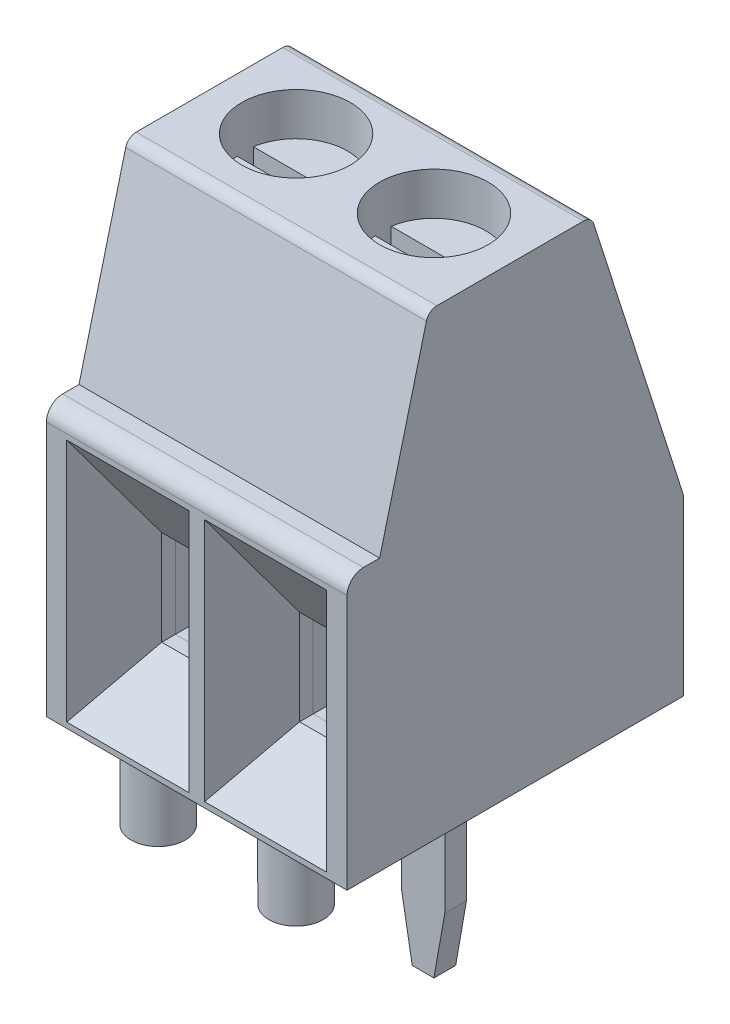
SolidWorks part; units mm, degrees
ref_plane "Plan de face" through (0, 0, 0) normal (0, 0, 1) x (1, 0, 0)
ref_plane "Plan de dessus" through (0, 0, 0) normal (0, 1, 0) x (1, 0, 0)
ref_plane "Plan de droite" through (0, 0, 0) normal (1, 0, 0) x (0, 0, -1)
sketch "Esquisse4" plane through (0, 0, 0) normal (1, 0, 0) x (0, 0, -1)
  line L0 (-3.1, 0) -> (3.1, 0)
  line L1 (3.1, 0) -> (3.1, 3.2)
  line L2 (3.1, 3.2) -> (1.4446, 8.3611)
  line L3 (1.2541, 8.5) -> (-1.4449, 8.5)
  line L4 (-1.6386, 8.3498) -> (-2.5, 5)
  line L5 (-2.5, 5) -> (-2.8, 5)
  line L6 (-3.1, 4.7) -> (-3.1, 0)
  arc A0 (-2.8, 5) -> (-3.1, 4.7) centre (-2.8, 4.7) ccw
  arc A1 (-1.4449, 8.5) -> (-1.6386, 8.3498) centre (-1.4449, 8.3) ccw
  arc A2 (1.4446, 8.3611) -> (1.2541, 8.5) centre (1.2541, 8.3) ccw
  point P11 (-3.1, 5)
  point P14 (-1.6, 8.5)
  point P17 (1.4, 8.5)
  dimension "D9" = 0.3
  dimension "D10" = 0.2
  dimension "D1" = 3.1
  dimension "D2" = 6.2
  dimension "D3" = 8.5
  dimension "D4" = 3.2
  dimension "D5" = 5
  dimension "D6" = 0.6
  dimension "D7" = 1.5
  dimension "D8" = 4.5
extrude "Extrusion2" add sketch "Esquisse4" along normal blind 2.77
sketch "Esquisse5" plane through (0, 0, 0) normal (0, -1, 0) x (1, 0, 0)
  line L0 (0, 3.1) -> (0, -3.1) construction
  line L1 (0.5, 1.6) -> (2.5, 1.6)
  line L2 (0.5, 1.6) -> (0.5, -1.65)
  line L3 (0.5, -1.65) -> (2.5, -1.65)
  line L4 (2.5, 1.6) -> (2.5, -1.65)
  line L5 (2.77, 3.1) -> (0, 3.1) construction
  point P4 (1.5, 1.6)
  dimension "D1" = 1.5
  dimension "D2" = 3.25
  dimension "D3" = 1.5
  dimension "D4" = 2
extrude "Extrusion3" cut sketch "Esquisse5" against normal blind 6.5
hole_wizard "Chambrage pour vis à tête hexagonale M31" positions "Esquisse3D1" profile "Esquisse6" counterbore size "M3" standard "ISO" end condition through all
sketch3d "Esquisse3D1"
  point P0 (1.5, 8.5, 0)
  dimension "D1" = 1.5
sketch "Esquisse6" plane through (1.5, 8.5, 0) normal (1, 0, 0) x (0, 0, 1)
  line L0 (0, 0) -> (0, 8.5)
  line L1 (0, 8.5) -> (0.75, 8.5)
  line L3 (0.75, 8.5) -> (0.75, 1.5)
  line L4 (0.75, 1.5) -> (1, 1.5)
  line L5 (1, 1.5) -> (1, 0)
  line L7 (1, 0) -> (0, 0)
  line L11 (0, -6.35) -> (0, 107.95) construction
  dimension "Diamètre du perçage jusqu'au prochain" = 1.5
  dimension "Profondeur du perçage jusqu'au prochain" = 8.5
  dimension "Diamètre du chambrage" = 2
  dimension "Profondeur du chambrage" = 1.5
sketch "Esquisse7" plane through (0, 0, 3.1) normal (0, 0, 1) x (1, 0, 0)
  line L0 (0, 4.7) -> (0, 0) construction
  line L1 (0.375, 4.6) -> (2.625, 4.6)
  line L2 (0.375, 4.6) -> (0.375, 0.1)
  line L3 (0.375, 0.1) -> (2.625, 0.1)
  line L4 (2.625, 4.6) -> (2.625, 0.1)
  line L5 (2.77, 0) -> (0, 0) construction
  point P4 (1.5, 0.1)
  dimension "D1" = 1.5
  dimension "D2" = 0.1
  dimension "D3" = 2.25
  dimension "D4" = 4.5
ref_plane "Plan1" through (0, 0, 1.85) normal (0, 0, -1) x (-1, 0, 0)
sketch "Esquisse8" plane through (0, 0, 1.85) normal (0, 0, -1) x (-1, 0, 0)
  line L1 (-0.875, 2.75) -> (-2.125, 2.75)
  line L2 (-0.875, 2.75) -> (-0.875, 1)
  line L3 (-0.875, 1) -> (-2.125, 1)
  line L4 (-2.125, 2.75) -> (-2.125, 1)
  line L5 (0, 4.7) -> (0, 0) construction
  line L6 (-2.77, 0) -> (0, 0) construction
  point P4 (-1.5, 1)
  dimension "D1" = 1.5
  dimension "D2" = 1.25
  dimension "D3" = 1.75
  dimension "D4" = 1
loft "Enlèvement de matière-Lissage1" cut profiles "Esquisse7", "Esquisse8" connector at (2.625, 0.1, 3.1) connector at (2.125, 1, 1.85)
extrude "Extrusion4" cut sketch "Esquisse8<2>" along normal up to next
sketch "Esquisse8<2>" plane through (0, 0, 1.85) normal (0, 0, -1) x (-1, 0, 0) same geometry as "Esquisse8"
chamfer "Chanfrein1" distance 0.5 angle 20 1 edges at (1.5, 0, 1.6) first distance on face at (1.5, 3.25, 1.6)
ref_plane "Plan2" through (1.5, 0, 0) normal (-1, 0, 0) x (0, 0, 1)
sketch "Esquisse9" plane through (1.5, 0, 0) normal (-1, 0, 0) x (0, 0, 1)
  line L0 (-1.65, 0) -> (-2.55, 0)
  line L1 (3.1, 0) -> (-3.1, 0) construction
  line L2 (-2.05, 3.75) -> (-2.05, 4.25)
  line L3 (-2.05, 4.25) -> (-1.65, 5.75)
  line L4 (-1.65, 6.5) -> (-1.65, 0) construction
  line L5 (-1.65, 5.75) -> (-1.65, 0)
  line L6 (-2.05, 3.75) -> (-2.15, 3.75)
  line L7 (-2.55, 3.35) -> (-2.55, 0)
  arc A0 (-2.15, 3.75) -> (-2.55, 3.35) centre (-2.15, 3.35) ccw
  point P13 (-2.55, 3.75)
  dimension "D6" = 0.4
  dimension "D1" = 0.4
  dimension "D2" = 5.75
  dimension "D3" = 4.25
  dimension "D4" = 0.5
  dimension "D5" = 3.75
extrude "Extrusion5" cut sketch "Esquisse9" against normal mid plane 1
chamfer "Chanfrein4" distance 0.5 angle 20 3 edges at (0.75, 0, -1.65) (2.25, 0, -1.65) (1.5, 0, -2.55) first distance on face at (1.5, 3.0625, -1.65) first distance on face at (1.5, 1.675, -2.55)
sketch "Esquisse10" plane through (1.5, 0, 0) normal (-1, 0, 0) x (0, 0, 1)
  line L0 (-2.55, 2.5) -> (-2.9, 1.25)
  line L1 (-2.55, 3.35) -> (-2.55, 0.5) construction
  line L2 (-2.9, 1.25) -> (-3.1, 1.25)
  line L3 (-3.1, 0) -> (-3.1, 3.2) construction
  line L4 (-3.1, 1.25) -> (-3.1, 3.2)
  line L5 (-3.1, 3.2) -> (-2.55, 4.9147)
  line L6 (-3.1, 3.2) -> (-1.4446, 8.3611) construction
  line L7 (-2.55, 4.9147) -> (-2.55, 2.5)
  line L8 (3.1, 0) -> (-3.1, 0) construction
  line L9 (-2.732, 0) -> (-1.832, 0) construction
  dimension "D1" = 1.25
  dimension "D2" = 2.5
  dimension "D3" = 0.2
extrude "Extrusion6" cut sketch "Esquisse10" against normal mid plane 1
sketch "Esquisse11" plane through (0, 0, 0) normal (0, -1, 0) x (1, 0, 0)
  line L0 (0, 3.1) -> (0, -3.1) construction
  circle A0 centre (1.5, 2.54) radius 0.5
  dimension "D3" = 1
  dimension "D1" = 2.54
  dimension "D2" = 1.5
extrude "Extrusion7" add sketch "Esquisse11" along normal blind 1.25
mirror "Symétrie1" about plane through (2.77, 8.3, -1.2541) normal (1, 0, 0) of bodies 120 118
sketch "Esquisse12" plane through (1.5, 0, 0) normal (-1, 0, 0) x (0, 0, 1)
  line L2 (0, -993) -> (0, 49007) construction
  line L3 (1, 7) -> (-1, 7) construction
  line L4 (-0.2, -3.5) -> (0.2, -3.5)
  line L5 (-0.2, -3.5) -> (-0.2, 0)
  line L7 (-1.832, 0) -> (1.782, 0) construction
  line L8 (-0.3, 0.1) -> (-2.05, 0.1)
  line L9 (-2.732, 0) -> (-1.832, 0) construction
  line L10 (-2.55, 0.6) -> (-2.55, 3.05)
  line L11 (-2.05, 3.55) -> (1.6, 3.55)
  line L12 (1.6, 6.5) -> (1.6, 0.5) construction
  line L13 (1.6, 3.55) -> (1.6, 3.15)
  line L14 (1.6, 3.15) -> (-2.05, 3.15)
  line L15 (-2.15, 3.05) -> (-2.15, 0.6)
  line L16 (-2.05, 0.5) -> (-0.3, 0.5)
  line L17 (0.2, 0) -> (0.2, -3.5)
  line L18 (-2.05, 3.75) -> (-2.15, 3.75) construction
  line L19 (-2.55, 2.5) -> (-2.55, 0.5) construction
  arc A0 (-2.15, 0.6) -> (-2.05, 0.5) centre (-2.05, 0.6) ccw
  arc A1 (-2.05, 3.15) -> (-2.15, 3.05) centre (-2.05, 3.05) ccw
  arc A2 (-0.2, 0) -> (-0.3, 0.1) centre (-0.3, 0) ccw
  arc A3 (-0.3, 0.5) -> (0.2, 0) centre (-0.3, 0) cw
  arc A4 (-2.05, 0.1) -> (-2.55, 0.6) centre (-2.05, 0.6) cw
  arc A5 (-2.55, 3.05) -> (-2.05, 3.55) centre (-2.05, 3.05) cw
  point P3 (0, -3.5)
  point P10 (0, 7)
  point P29 (-0.2, 0)
  point P34 (-2.55, 0)
  dimension "D5" = 0.1
  dimension "D6" = 0.5
  dimension "D1" = 0.4
  dimension "D2" = 0.4
  dimension "D3" = 0.4
  dimension "D4" = 0.4
  dimension "D7" = 0.1
  dimension "D8" = 3.5
  dimension "D9" = 0.2
  dimension "D10" = 0
extrude "Extrusion8" add sketch "Esquisse12" along normal mid plane 0.8 separate body
chamfer "Chanfrein5" distance 0.2 angle 80 2 edges at (1.9, -3.5, 0) (1.1, -3.5, 0) first distance on face at (1.5, -3.5, 0)
sketch "Esquisse13" plane through (0, 0, 1.6) normal (0, 0, -1) x (-1, 0, 0)
  line L0 (-2.5, 6.5) -> (-2.5, 0.5) construction
  line L1 (-2.5, 4.7) -> (-0.5, 4.7)
  line L2 (-2.5, 4.7) -> (-2.5, 0.5)
  line L3 (-2.5, 0.5) -> (-0.5, 0.5)
  line L4 (-0.5, 4.7) -> (-0.5, 0.5)
  line L5 (-2.5, 0.5) -> (-0.5, 0.5) construction
  line L6 (-0.5, 0.5) -> (-0.5, 0) construction
  line L7 (-0.875, 1) -> (-2.125, 1) construction
  line L8 (-2.125, 1) -> (-0.875, 1)
  line L9 (-2.125, 1) -> (-2.125, 3.7)
  line L10 (-2.125, 3.7) -> (-0.875, 3.7)
  line L11 (-0.875, 1) -> (-0.875, 3.7)
  line L12 (-2.125, 1) -> (-2.125, 2.75) construction
  line L13 (-0.875, 2.75) -> (-0.875, 1) construction
  dimension "D1" = 1
  dimension "D2" = 2.7
extrude "Extrusion9" add sketch "Esquisse13" along normal blind 3 separate body
hole_wizard "Trou taraudé M1.61" positions "Esquisse15" profile "Esquisse14" tap size "M1.6" standard "ISO"
sketch "Esquisse15" plane through (0, 4.7, 0) normal (0, 1, 0) x (-1, 0, 0)
  line L0 (0, -1.2541) -> (0, 1.4449) construction
  point P0 (-1.5, 0)
  dimension "D1" = 1.5
sketch "Esquisse14" plane through (1.5, 4.7, 0) normal (1, 0, 0) x (0, 0, 1)
  line L0 (0, 0) -> (0, 3.4255)
  line L1 (0, 3.4255) -> (0.625, 3.05)
  line L2 (0.625, 3.05) -> (0.625, 0)
  line L5 (0.625, 0) -> (0, 0)
  line L10 (0, 3.4255) -> (-0.625, 3.05) construction
  line L11 (0, -6.35) -> (0, 107.95) construction
  dimension "Diamètre du trou pour taraudage" = 1.25
  dimension "Profondeur du trou pour taraudage" = 3.05
  dimension "Angle de pointe" = 118
cosmetic thread "Filetage de perçage1" parameters "D1"=1, "D2"=1.6
sketch "Esquisse16" plane through (0, 7, 0) normal (0, 1, 0) x (1, 0, 0)
  circle A0 centre (1.5, 0) radius 0.95
  dimension "D1" = 1.9
extrude "Extrusion10" add sketch "Esquisse16" along normal blind 0.75 separate body
sketch "Esquisse17" plane through (0, 7.75, 0) normal (0, 1, 0) x (1, 0, 0)
  line L1 (0.55, 0.15) -> (2.45, 0.15)
  line L2 (0.55, 0.15) -> (0.55, -0.15)
  line L3 (0.55, -0.15) -> (2.45, -0.15)
  line L4 (2.45, 0.15) -> (2.45, -0.15)
  circle A0 centre (1.5, 0) radius 0.95 construction
  point P4 (0.55, 0)
  dimension "D1" = 0.3
extrude "Extrusion11" cut sketch "Esquisse17" against normal blind 0.3
sketch "Esquisse18" plane through (0, 7, 0) normal (0, -1, 0) x (1, 0, 0)
  circle A0 centre (1.5, 0) radius 0.7
  dimension "D1" = 1.4
extrude "Extrusion12" add sketch "Esquisse18" along normal blind 3.3
pattern_linear "Répétition linéaire1" count 2 spacing 2.54 along (1, 0, 0) of bodies 127 123 121
